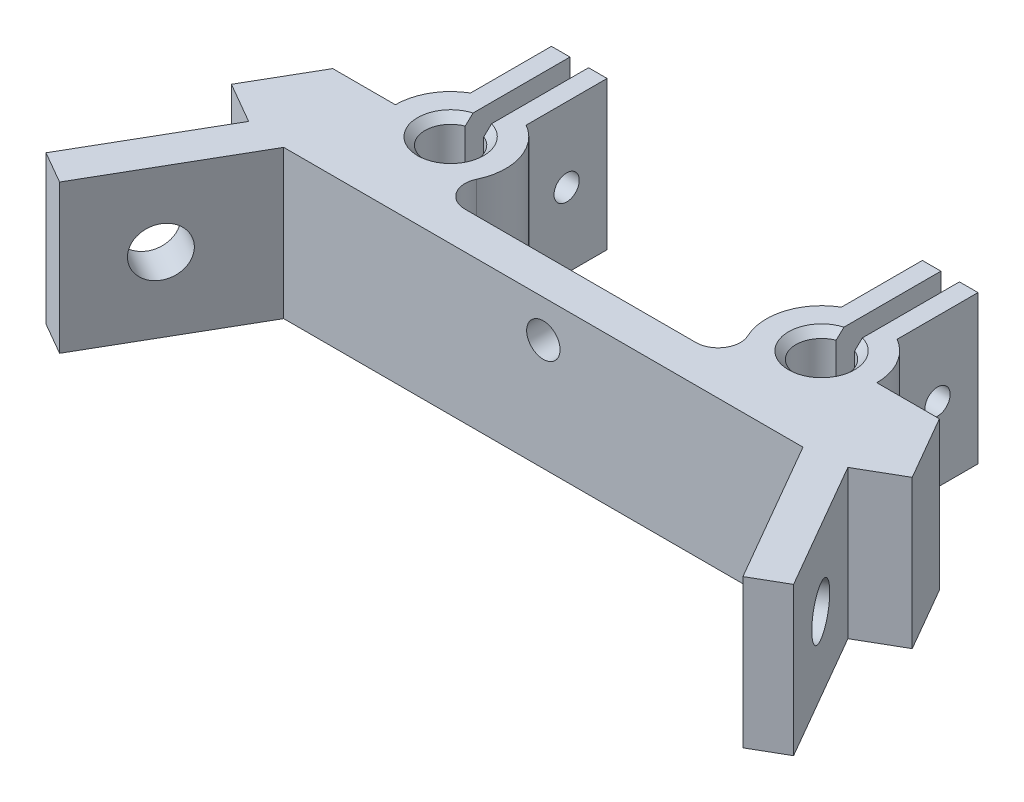
SolidWorks part; units mm, degrees
ref_plane "Front Plane" through (0, 0, 0) normal (0, 0, 1) x (1, 0, 0)
ref_plane "Top Plane" through (0, 0, 0) normal (0, 1, 0) x (1, 0, 0)
ref_plane "Right Plane" through (0, 0, 0) normal (1, 0, 0) x (0, 0, -1)
sketch "Sketch1" plane through (0, 0, 0) normal (0, 1, 0) x (1, 0, 0)
  line L0 (0, 116.7614) -> (0, -100.8523) construction
  line L1 (23.75, 120.7156) -> (23.75, 134.8444)
  line L2 (28.75, 134.8444) -> (28.75, 123.9374)
  line L3 (25, -2.1466) -> (25, 14.9187) construction
  line L4 (23.75, 134.8444) -> (21.25, 134.8444)
  line L5 (21.25, 134.8444) -> (21.25, 123.9374)
  line L6 (26.25, 134.8444) -> (28.75, 134.8444)
  line L7 (26.25, 120.7156) -> (26.25, 134.8444)
  line L8 (-25, -0.2491) -> (-25, 16.8161) construction
  line L9 (-26.25, 120.7156) -> (-26.25, 134.8444)
  line L10 (-26.25, 134.8444) -> (-28.75, 134.8444)
  line L11 (-21.25, 134.8444) -> (-21.25, 123.9374)
  line L12 (-23.75, 134.8444) -> (-21.25, 134.8444)
  line L13 (-28.75, 134.8444) -> (-28.75, 123.9374)
  line L14 (-23.75, 120.7156) -> (-23.75, 134.8444)
  line L15 (-15.5685, 110) -> (15.5685, 110)
  line L16 (-35, 105) -> (35, 105)
  line L17 (-32.45, 117.5) -> (-40.889, 117.5)
  line L18 (0, 110) -> (-95.2628, -55) construction
  line L19 (-95.2628, -55) -> (95.2628, -55) construction
  line L20 (95.2628, -55) -> (0, 110) construction
  line L21 (-40.889, 117.5) -> (-45.889, 108.8397)
  line L22 (-50.3897, 88.3442) -> (-46.0596, 85.8442)
  line L23 (-46.0596, 85.8442) -> (-35, 105)
  line L24 (46.0596, 85.8442) -> (35, 105)
  line L25 (50.3897, 88.3442) -> (46.0596, 85.8442)
  line L26 (50.3897, 88.3442) -> (40.3897, 105.6647)
  line L27 (32.45, 117.5) -> (40.889, 117.5)
  line L28 (-50.3897, 88.3442) -> (-40.3897, 105.6647)
  line L29 (-40.3897, 105.6647) -> (-45.889, 108.8397)
  line L30 (40.3897, 105.6647) -> (45.889, 108.8397)
  line L31 (40.889, 117.5) -> (45.889, 108.8397)
  arc A0 (21.25, 123.9374) -> (18.2761, 114.2919) centre (25, 117.5) ccw
  arc A1 (23.75, 120.7156) -> (26.25, 120.7156) centre (25, 117.5) ccw
  arc A2 (-23.75, 120.7156) -> (-26.25, 120.7156) centre (-25, 117.5) cw
  arc A3 (-21.25, 123.9374) -> (-18.2761, 114.2919) centre (-25, 117.5) cw
  circle A4 centre (0, 0) radius 110 construction
  circle A5 centre (0, 0) radius 55 construction
  arc A6 (15.5685, 110) -> (18.2761, 114.2919) centre (15.5685, 113) ccw
  arc A7 (-18.2761, 114.2919) -> (-15.5685, 110) centre (-15.5685, 113) ccw
  arc A8 (-28.75, 123.9374) -> (-32.45, 117.5) centre (-25, 117.5) ccw
  arc A9 (28.75, 123.9374) -> (32.45, 117.5) centre (25, 117.5) cw
  point P12 (23.75, 124.8444)
  point P13 (26.25, 124.8444)
  point P27 (-26.25, 124.8444)
  point P28 (-23.75, 124.8444)
  point P67 (0, 0)
  dimension "D2" = 6.9
  dimension "D3" = 4
  dimension "D5" = 2.5
  dimension "D10" = 120
  dimension "D11" = 10
  dimension "D7" = 220
  dimension "D13" = 3
  dimension "D14" = 7.5
  dimension "D1" = 50
  dimension "D4" = 10
  dimension "D6" = 2.5
  dimension "D8" = 5
  dimension "D9" = 70
  dimension "D12" = 5
  dimension "D15" = 20
  dimension "D16" = 6.35
extrude "Boss-Extrude1" add sketch "Sketch1" along normal blind 20 contours A3 L11 L12 L14 A2 L9 L10 L13 | A1 L1 L4 L5 A0 L2 L6 L7 | L15 A3 L16 A0 region at (25, 0, -112.9294)
sketch "Sketch2" plane through (0, 0, 0) normal (1, 0, 0) x (0, 0, -1)
  line L0 (123.9374, 20) -> (123.9374, 0) construction
  line L3 (134.8444, 10) -> (123.9374, 10) construction
  line L4 (134.8444, 20) -> (134.8444, 0) construction
  circle A0 centre (129.3909, 10) radius 1.7
  dimension "D1" = 3.4
extrude "Cut-Extrude1" cut sketch "Sketch2" against normal mid plane 57.5
sketch "Sketch4" plane through (0, 0, -105) normal (0, 0, 1) x (1, 0, 0)
  line L0 (-35, 20) -> (35, 20) construction
  circle A0 centre (0, 15) radius 2.25
  point P2 (0, 20)
  dimension "D2" = 5
  dimension "D1" = 4.5
extrude "Cut-Extrude2" cut sketch "Sketch4" against normal up to next contours A0 region at (0, 15, -105)
chamfer "Chamfer1" distance 1 angle 45 2 edges at (25, 20, -114.05) (-25, 20, -114.05)
sketch "Sketch5" plane through (-76.0465, 0, -43.9054) normal (-0.866, 0, -0.5) x (-0.5, 0, 0.866)
  line L0 (-51.3135, 10) -> (-71.3135, 10) construction
  line L1 (-51.3135, 20) -> (-51.3135, 0) construction
  line L2 (-71.3135, 20) -> (-71.3135, 0) construction
  circle A1 centre (-61.3135, 10) radius 3.3
  dimension "D1" = 6.6
extrude "Cut-Extrude3" cut sketch "Sketch5" against normal up to next
mirror "Mirror1" about plane through (0, 0, 0) normal (1, 0, 0) of "Cut-Extrude3"
equation "\"RodSpacing\"= 50"
equation "\"D1@Sketch1\"=\"RodSpacing\""
equation "\"Clamp_Gap\"=2.5"
equation "\"D5@Sketch1\"=\"Clamp_Gap\""
equation "\"D6@Sketch1\"=\"Clamp_Gap\""
equation "\"D1@Cut-Extrude1\"=\"RodSpacing\"+(3*\"Clamp_Gap\")"
equation "\"Smooth_Rod_Hole\"=6.9"
equation "\"D2@Sketch1\"=\"Smooth_Rod_Hole\""
equation "\"Inside_Spacing\"=70"
equation "\"D9@Sketch1\"=\"Inside_Spacing\""
